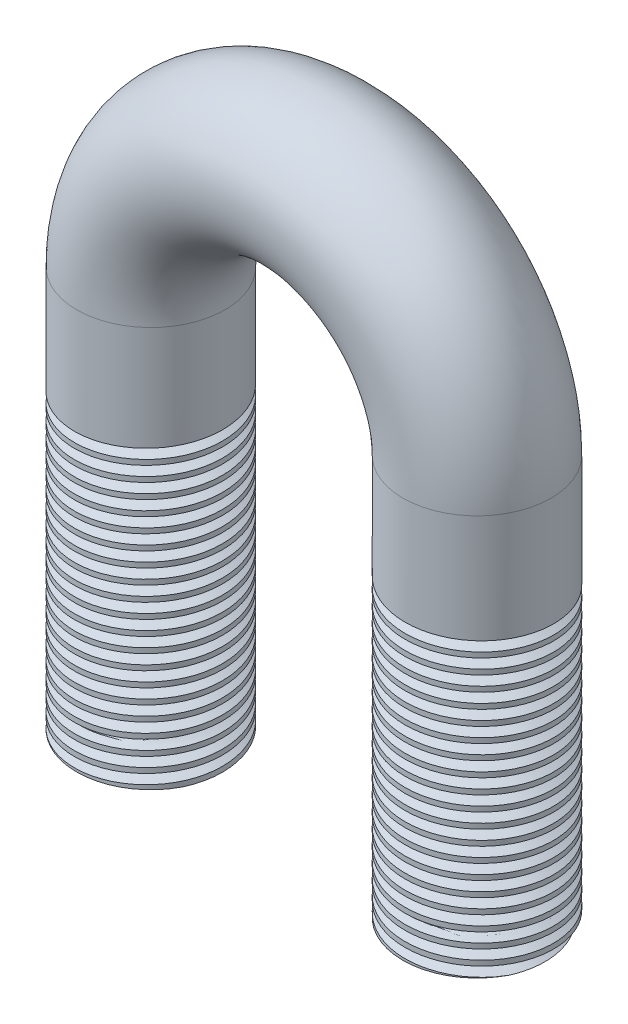
SolidWorks part; units mm, degrees
material "AISI 1020"
ref_plane "Plano frontal" through (0, 0, 0) normal (0, 0, 1) x (1, 0, 0)
ref_plane "Plano superior" through (0, 0, 0) normal (0, 1, 0) x (1, 0, 0)
ref_plane "Plano direito" through (0, 0, 0) normal (1, 0, 0) x (0, 0, -1)
sketch "Esboço2" plane through (0, 0, 0) normal (0, 0, 1) x (1, 0, 0)
  line L0 (-5.5, 0) -> (0, 0) construction
  line L1 (0, 5.5) -> (0, -13.5) construction
  line L2 (-5.5, 0) -> (-5.5, -13.5)
  arc A0 (0, 5.5) -> (-5.5, 0) centre (0, 0) ccw
  dimension "D1" = 11
  dimension "D2" = 19
sweep "Varredura1" add path "Esboço2" circular profile diameter 5 parameters "D3"=5
sketch "Esboço19" plane through (0, -13.5, 0) normal (0, -1, 0) x (1, 0, 0)
  circle A0 centre (-5.5, 0) radius 2.5 construction
  circle A1 centre (-5.5, 0) radius 2.5
curve "Hélice/Espiral3" pitch 0.5 height 10 radius 2.5 centre (-5.5, -13.5, 0) axis (0, 1, 0) start towards (0, 0, -1)
ref_plane "Plano1" through (-5.5, 0, 0) normal (1, 0, 0) x (0, 0, -1)
sketch "Esboço20" plane through (-5.5, 0, 0) normal (1, 0, 0) x (0, 0, -1)
  line L4 (0, 4.4358) -> (0, -4.4358) construction
  line L5 (2.2171, -13.5) -> (2.6415, -13.745)
  line L6 (2.6415, -13.745) -> (2.6415, -13.255)
  line L7 (2.6415, -13.255) -> (2.2171, -13.5)
  circle A0 centre (2.5, -13.5) radius 0.1415 construction
  dimension "D1" = 0.49
sweep "Varredura de corte3" cut profiles "Esboço20" path "Hélice/Espiral3" align with end faces yes
mirror "Espelhar1" about plane through (0, 0, 0) normal (1, 0, 0) of "Varredura1", "Varredura de corte3"
